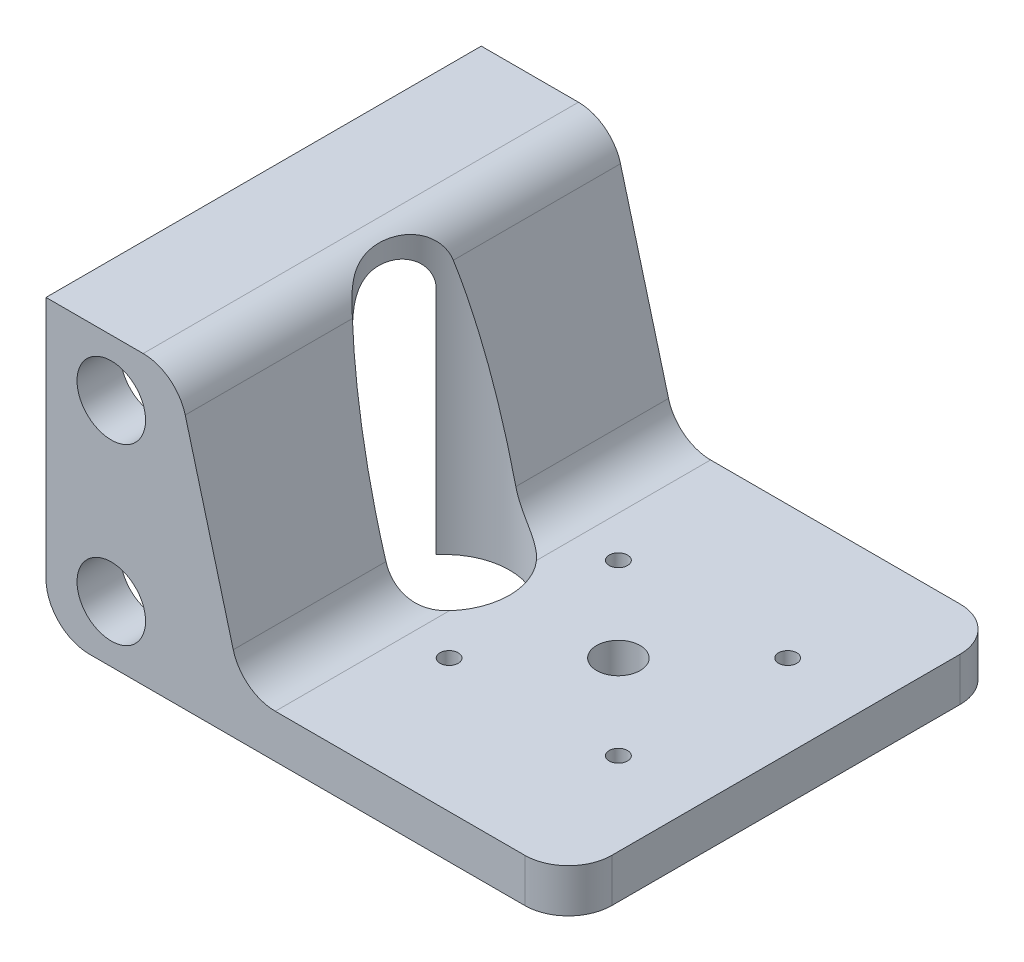
SolidWorks part; units mm, degrees
ref_plane "Front" through (0, 0, 0) normal (0, 0, 1) x (1, 0, 0)
ref_plane "Top" through (0, 0, 0) normal (0, 1, 0) x (1, 0, 0)
ref_plane "Right" through (0, 0, 0) normal (1, 0, 0) x (0, 0, -1)
sketch "Sketch1" plane through (0, 0, 0) normal (0, 0, 1) x (1, 0, 0)
  line L1 (-15, 13) -> (15, 13)
  line L2 (-15, 13) -> (-15, -53)
  line L3 (-15, -53) -> (15, -53)
  line L4 (15, 13) -> (15, -53)
  circle A0 centre (0, 0) radius 7.875
  circle A1 centre (0, -40) radius 7.875
  point P9 (0, 13)
  dimension "D1" = 15.75
  dimension "D2" = 40
  dimension "D3" = 13
  dimension "D4" = 13
  dimension "D5" = 30
extrude "Boss-Extrude1" add sketch "Sketch1" along normal mid plane 100
sketch "Sketch2" plane through (15, 0, 0) normal (1, 0, 0) x (0, 0, -1)
  line L0 (-50, -53) -> (50, -53) construction
  line L1 (-40, -53) -> (40, -53)
  line L2 (-40, -53) -> (-40, 10)
  line L3 (-40, 10) -> (40, 10)
  line L4 (40, -53) -> (40, 10)
  line L5 (-50, 13) -> (50, 13) construction
  point P8 (0, 10)
  dimension "D1" = 3
  dimension "D2" = 80
extrude "Cut-Extrude1" cut sketch "Sketch2" against normal through all
sketch "Sketch4" plane through (0, 0, 50) normal (0, 0, 1) x (1, 0, 0)
  line L0 (15, 13) -> (30.0052, -43)
  line L1 (30.0052, -43) -> (105, -43)
  line L2 (105, -43) -> (105, -53)
  line L3 (105, -53) -> (15, -53)
  line L4 (15, -53) -> (15, 13)
  dimension "D1" = 10
  dimension "D2" = 15
  dimension "D3" = 90
extrude "Boss-Extrude2" add sketch "Sketch4" against normal up to vertex (100 mm away) up to point (15, -53, -50)
sketch "Sketch5" plane through (0, -43, 0) normal (0, 1, 0) x (1, 0, 0)
  line L0 (15, -50) -> (15, 50) construction
  circle A0 centre (66.5, 0) radius 5
  dimension "D2" = 10
  dimension "D1" = 51.5
extrude "Cut-Extrude2" cut sketch "Sketch5" against normal through all
hole_wizard "M5x0.8 Tapped Hole1" positions "Sketch7" profile "Sketch8" tap size "M5x0.8" standard "ANSI Metric" end condition through all
sketch "Sketch7" plane through (0, -43, 0) normal (0, 1, 0) x (1, 0, 0)
  line L0 (66.5, 0) -> (66.5, 27.5) construction
  line L3 (47.0546, -19.4454) -> (85.9454, 19.4454) construction
  line L6 (85.9454, -19.4454) -> (47.0546, 19.4454) construction
  circle A0 centre (66.5, 0) radius 27.5 construction
  point P0 (85.9454, 19.4454)
  point P21 (85.9454, -19.4454)
  point P22 (47.0546, 19.4454)
  point P27 (47.0546, -19.4454)
  dimension "D1" = 55
  dimension "D2" = 45
  dimension "D3" = 45
sketch "Sketch8" plane through (85.9454, -43, -19.4454) normal (1, 0, 0) x (0, 0, 1)
  line L0 (0, 0) -> (0, 10.0001)
  line L1 (0, 10.0001) -> (2.1, 10.0001)
  line L2 (2.1, 10.0001) -> (2.1, 0)
  line L5 (2.1, 0) -> (0, 0)
  line L11 (0, -6.35) -> (0, 107.95) construction
  dimension "Thread Major Dia." = 4.2
  dimension "Thru Tap Drill Depth" = 10.0001
fillet "Fillet1" radius 10 7 edges at (15, 13, 0) (30.0052, -43, 0) (105, -48, -50) (105, -48, 50) (-15, -53, -45) (-15, -53, 45) (15, 10, 0)
sketch "Sketch10" plane through (0, 13, 0) normal (0, 1, 0) x (1, 0, 0)
  line L0 (-15, -50) -> (-15, 50) construction
  circle A0 centre (26.5, 0) radius 15
  dimension "D2" = 30
  dimension "D1" = 41.5
extrude "Cut-Extrude3" cut sketch "Sketch10" against normal through all
